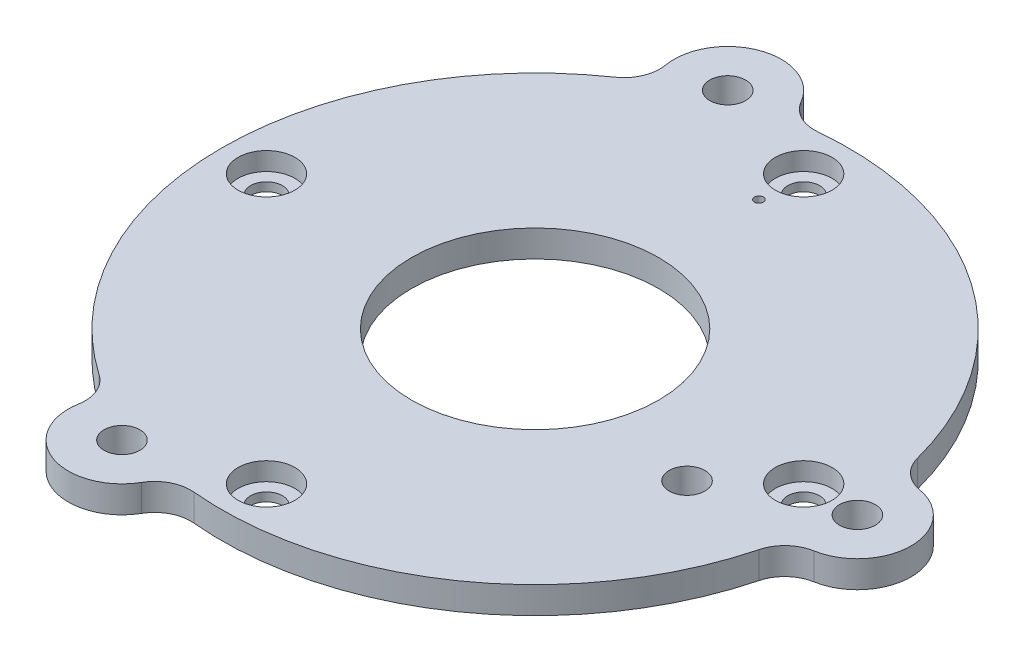
SolidWorks part; units mm, degrees
material "1060 Alloy"
ref_plane "Front Plane" through (0, 0, 0) normal (0, 0, 1) x (1, 0, 0)
ref_plane "Top Plane" through (0, 0, 0) normal (0, 1, 0) x (1, 0, 0)
ref_plane "Right Plane" through (0, 0, 0) normal (1, 0, 0) x (0, 0, -1)
sketch "Sketch1" plane through (0, 0, 0) normal (0, 1, 0) x (1, 0, 0)
  circle A0 centre (0, 0) radius 17.5
  dimension "D1" = 35
extrude "Boss-Extrude1" add sketch "Sketch1" along normal blind 1.5
sketch "Sketch6" plane through (0, 1.5, 0) normal (0, 1, 0) x (1, 0, 0)
  line L0 (0, 0) -> (19.3341, -5.1806) construction
  line L1 (0, 0) -> (17.9741, 0) construction
  circle A0 centre (0, 12.5) radius 0.25
  circle A1 centre (11.5911, -3.1058) radius 1
  dimension "D1" = 12.5
  dimension "D3" = 0.5
  dimension "D4" = 2
  dimension "D2" = 0
  dimension "D5" = 12
  dimension "D6" = 15
extrude "Cut-Extrude1" cut sketch "Sketch6" against normal through all both and the other way through all
hole_wizard "CBORE for #0 Socket Head Cap Screw1" positions "Sketch7" profile "Sketch8" counterbore size "#0" standard "ANSI Inch" end condition through all
sketch "Sketch7" plane through (0, 1.5, 0) normal (0, 1, 0) x (1, 0, 0)
  point P0 (0, 15)
  point P2 (-15, 0)
  point P4 (0, -15)
  point P6 (15, 0)
  dimension "D1" = 15
  dimension "D2" = 15
  dimension "D3" = 15
  dimension "D4" = 15
sketch "Sketch8" plane through (0, 1.5, -15) normal (1, 0, 0) x (0, 0, 1)
  line L0 (0, 0) -> (0, 1.5)
  line L1 (0, 1.5) -> (0.889, 1.5)
  line L3 (0.889, 1.5) -> (0.889, 1.016)
  line L4 (0.889, 1.016) -> (1.5875, 1.016)
  line L5 (1.5875, 1.016) -> (1.5875, 0)
  line L7 (1.5875, 0) -> (0, 0)
  line L11 (0, -6.35) -> (0, 107.95) construction
  dimension "Thru Hole Dia." = 1.778
  dimension "Thru Hole Depth" = 1.5
  dimension "C'Bore Dia." = 3.175
  dimension "C'Bore Depth" = 1.016
sketch "Sketch9" plane through (0, 0, 0) normal (0, -1, 0) x (1, 0, 0)
  line L0 (-6.1564, 16.9145) -> (0, 0) construction
  line L1 (0, 0) -> (-6.1564, -16.9145) construction
  line L2 (-6.1564, -16.9145) -> (0, 0) construction
  line L3 (0, 0) -> (18, 0) construction
  line L4 (-3.2616, 17.702) -> (2.8948, 0.7876)
  line L5 (-8.8801, 15.6571) -> (-2.7238, -1.2574)
  line L6 (17.75, 2.9896) -> (-0.25, 2.9896)
  line L7 (17.75, -2.9896) -> (-0.25, -2.9896)
  line L8 (-8.8801, -15.6571) -> (-2.7238, 1.2574)
  line L9 (-3.2616, -17.702) -> (2.8948, -0.7876)
  circle A0 centre (0, 0) radius 18
  circle A1 centre (-6.1564, 16.9145) radius 1
  circle A2 centre (-6.1564, -16.9145) radius 1
  circle A3 centre (18, 0) radius 1
  circle A4 centre (18, 0) radius 3
  circle A5 centre (-6.1564, -16.9145) radius 3
  circle A6 centre (-6.1564, 16.9145) radius 3
  circle A7 centre (0, 0) radius 3
  circle M10 centre (0, 0) radius 17.5
  dimension "D1" = 2
  dimension "D2" = 2
  dimension "D3" = 2
  dimension "D4" = 36
  dimension "D7" = 6
  dimension "D8" = 6
  dimension "D9" = 6
  dimension "D10" = 6
  dimension "D5" = 140
  dimension "D6" = 110
extrude "Boss-Extrude2" add sketch "Sketch9" against normal up to surface (1.5 mm away) contours A0 A4 A3 | A4 L6 M10 | A4 L7 M10 | A0 A5 A2 | A0 A5 A2 M10 | A5 L9 M10 | A5 L8 M10 | A0 A6 A1 | A6 A0 A1 M10 | A6 L4 M10 | A6 L5 M10 | A5 A0 A2 M10 | A0 A5 A2 M10 | A4 A0 A3 M10 | A0 A4 A3 M10 | A0 A6 A1 M10 | A6 A0 A1 M10 region at (-4.194, 0, 17.2363) region at (-6.6097, 0, 18.1601) region at (-3.1659, 0, 17.3639) region at (17.3995, 0, 2.9638) region at (19.3255, 0, 0) region at (17.6312, 0, 1.9541) region at (-8.7361, 0, 15.3365) region at (-7.8665, 0, 15.8996) region at (-7.8665, 0, -15.8996) region at (-6.6097, 0, -18.1601) region at (-8.7361, 0, -15.3365) region at (17.6312, 0, -1.9541) region at (17.3995, 0, -2.9638) region at (-3.1659, 0, -17.3639) region at (-4.194, 0, -17.2363) up to face at (0, 1.5, -13.4125)
fillet "Fillet1" radius 2 6 edges at (17.2428, 0.75, 2.9896) (-3.0881, 0.75, 17.2254) (-8.7066, 0.75, 15.1804) (-8.7066, 0.75, -15.1804) (-3.0881, 0.75, -17.2254) (17.2428, 0.75, -2.9896)
sketch "Sketch10" plane through (0, 1.5, 0) normal (0, 1, 0) x (1, 0, 0)
  circle A0 centre (-6.1564, 16.9145) radius 1
  circle A1 centre (18, 0) radius 1
  circle A2 centre (-6.1564, -16.9145) radius 1
extrude "Cut-Extrude2" cut sketch "Sketch10" against normal blind 10
sketch "Sketch11" plane through (0, 1.5, 0) normal (0, 1, 0) x (1, 0, 0)
  circle A0 centre (0, 0) radius 6.9
  dimension "D1" = 13.8
extrude "Cut-Extrude3" cut sketch "Sketch11" against normal blind 10
